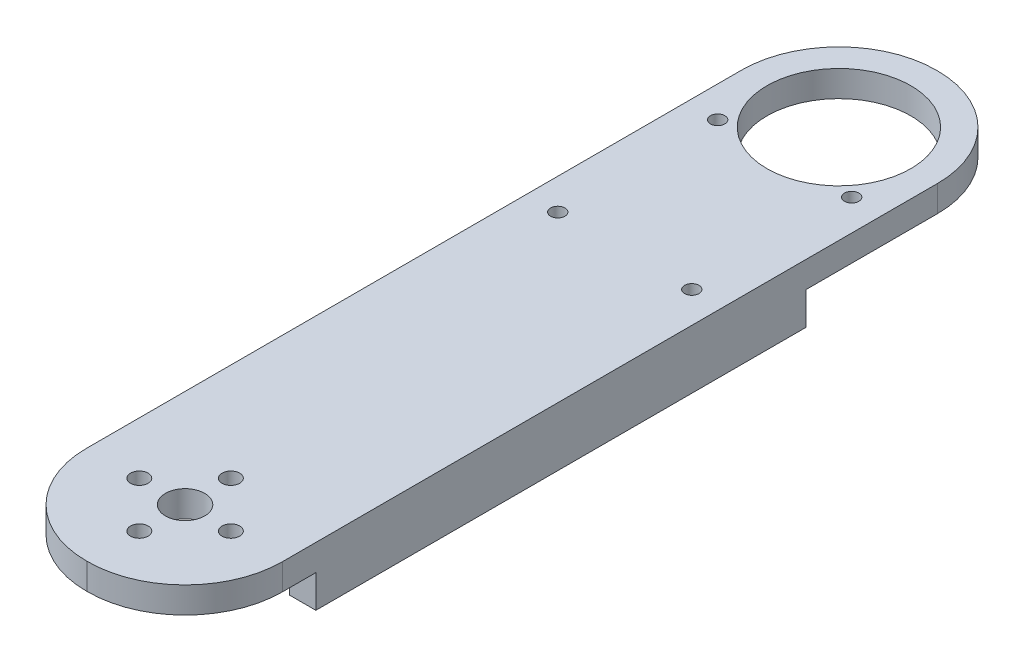
SolidWorks part; units mm, degrees
ref_plane "Front Plane" through (0, 0, 0) normal (0, 0, 1) x (1, 0, 0)
ref_plane "Top Plane" through (0, 0, 0) normal (0, 1, 0) x (1, 0, 0)
ref_plane "Right Plane" through (0, 0, 0) normal (1, 0, 0) x (0, 0, -1)
ref_plane "PY_m22_625" through (0, -22.625, 0) normal (0, 1, 0) x (1, 0, 0)
sketch "S_prism1" plane through (0, -22.625, 0) normal (0, 1, 0) x (1, 0, 0)
  line L0 (-0.1, -15) -> (0.1, -15)
  line L1 (15, -0.1) -> (15, 100.1)
  line L2 (0.1, 115) -> (-0.1, 115)
  line L3 (-15, 100.1) -> (-15, -0.1)
  arc A0 (-15, -0.1) -> (-0.1, -15) centre (-0.1, -0.1) ccw
  arc A1 (0.1, -15) -> (15, -0.1) centre (0.1, -0.1) ccw
  arc A2 (15, 100.1) -> (0.1, 115) centre (0.1, 100.1) ccw
  arc A3 (-0.1, 115) -> (-15, 100.1) centre (-0.1, 100.1) ccw
extrude "Boss_1" add sketch "S_prism1" along normal blind 4
ref_plane "PZ_m80_000" through (0, 0, -80) normal (0, 0, 1) x (1, 0, 0)
sketch "S_box2" plane through (0, 0, -80) normal (0, 0, 1) x (1, 0, 0)
  line L0 (-15, -27.625) -> (-11, -27.625)
  line L1 (-11, -27.625) -> (-11, -22.125)
  line L2 (-11, -22.125) -> (-15, -22.125)
  line L3 (-15, -22.125) -> (-15, -27.625)
  dimension "P1" = 15
  dimension "P2" = 27.625
  dimension "P3" = 11
  dimension "P4" = 27.625
  dimension "P5" = 11
  dimension "P6" = 22.125
  dimension "P7" = 15
  dimension "P8" = 22.125
extrude "Boss_2" add sketch "S_box2" along normal blind 75
sketch "S_box3" plane through (0, 0, -80) normal (0, 0, 1) x (1, 0, 0)
  line L0 (11, -27.625) -> (15, -27.625)
  line L1 (15, -27.625) -> (15, -22.125)
  line L2 (15, -22.125) -> (11, -22.125)
  line L3 (11, -22.125) -> (11, -27.625)
  dimension "P1" = 11
  dimension "P2" = 27.625
  dimension "P3" = 15
  dimension "P4" = 27.625
  dimension "P5" = 15
  dimension "P6" = 22.125
  dimension "P7" = 11
  dimension "P8" = 22.125
extrude "Boss_3" add sketch "S_box3" along normal blind 75
ref_plane "PY_m22_725" through (0, -22.725, 0) normal (0, 1, 0) x (1, 0, 0)
sketch "S_hole4" plane through (0, -22.725, 0) normal (0, 1, 0) x (1, 0, 0)
  circle A0 centre (0, 0) radius 3
  dimension "D1_S_hole4" = 6
extrude "Hole_4" cut sketch "S_hole4" along normal blind 4.2
sketch "S_hole5" plane through (0, -22.725, 0) normal (0, 1, 0) x (1, 0, 0)
  circle A0 centre (7, 0) radius 1.35
  dimension "D1_S_hole5" = 2.7
  dimension "P2" = 7
extrude "Hole_5" cut sketch "S_hole5" along normal blind 4.2
sketch "S_hole6" plane through (0, -22.725, 0) normal (0, 1, 0) x (1, 0, 0)
  circle A0 centre (0, -7) radius 1.35
  dimension "D1_S_hole6" = 2.7
  dimension "P2" = 7
extrude "Hole_6" cut sketch "S_hole6" along normal blind 4.2
sketch "S_hole7" plane through (0, -22.725, 0) normal (0, 1, 0) x (1, 0, 0)
  circle A0 centre (-7, 0) radius 1.35
  dimension "D1_S_hole7" = 2.7
  dimension "P2" = 7
extrude "Hole_7" cut sketch "S_hole7" along normal blind 4.2
sketch "S_hole8" plane through (0, -22.725, 0) normal (0, 1, 0) x (1, 0, 0)
  circle A0 centre (0, 7) radius 1.35
  dimension "D1_S_hole8" = 2.7
  dimension "P2" = 7
extrude "Hole_8" cut sketch "S_hole8" along normal blind 4.2
sketch "S_hole9" plane through (0, -22.725, 0) normal (0, 1, 0) x (1, 0, 0)
  circle A0 centre (0, 100) radius 11
  dimension "D1_S_hole9" = 22
  dimension "P2" = 100
extrude "Hole_9" cut sketch "S_hole9" along normal blind 4.2
sketch "S_hole10" plane through (0, -22.725, 0) normal (0, 1, 0) x (1, 0, 0)
  circle A0 centre (-10.25, 91.7) radius 1.1
  dimension "D1_S_hole10" = 2.2
  dimension "P2" = 10.25
  dimension "P3" = 91.7
extrude "Hole_10" cut sketch "S_hole10" along normal blind 4.2
sketch "S_hole11" plane through (0, -22.725, 0) normal (0, 1, 0) x (1, 0, 0)
  circle A0 centre (10.25, 91.7) radius 1.1
  dimension "D1_S_hole11" = 2.2
  dimension "P2" = 10.25
  dimension "P3" = 91.7
extrude "Hole_11" cut sketch "S_hole11" along normal blind 4.2
sketch "S_hole12" plane through (0, -22.725, 0) normal (0, 1, 0) x (1, 0, 0)
  circle A0 centre (-10.25, 67.25) radius 1.1
  dimension "D1_S_hole12" = 2.2
  dimension "P2" = 10.25
  dimension "P3" = 67.25
extrude "Hole_12" cut sketch "S_hole12" along normal blind 4.2
sketch "S_hole13" plane through (0, -22.725, 0) normal (0, 1, 0) x (1, 0, 0)
  circle A0 centre (10.25, 67.25) radius 1.1
  dimension "D1_S_hole13" = 2.2
  dimension "P2" = 10.25
  dimension "P3" = 67.25
extrude "Hole_13" cut sketch "S_hole13" along normal blind 4.2
equation "\"plate_t\" = 3"
equation "\"clearance\" = 0.4"
